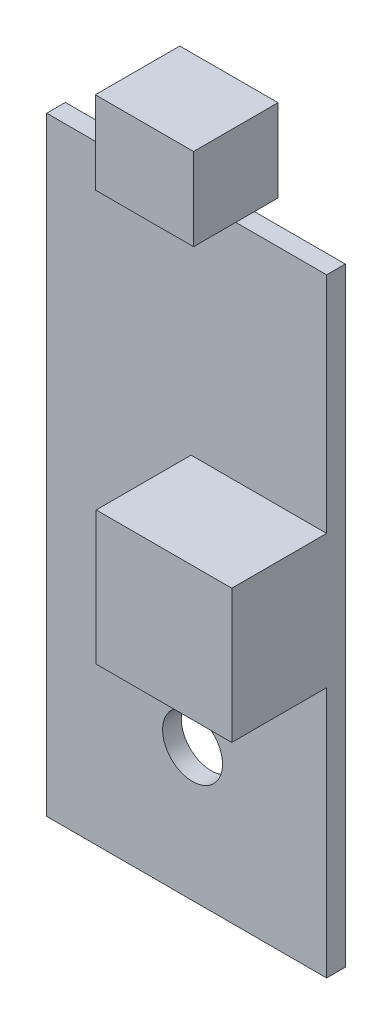
SolidWorks part; units mm, degrees
ref_plane "Front Plane" through (0, 0, 0) normal (0, 0, 1) x (1, 0, 0)
ref_plane "Top Plane" through (0, 0, 0) normal (0, 1, 0) x (1, 0, 0)
ref_plane "Right Plane" through (0, 0, 0) normal (1, 0, 0) x (0, 0, -1)
sketch "Sketch1" plane through (0, 0, 0) normal (0, 0, 1) x (1, 0, 0)
  line L0 (-7.125, 15.5) -> (-2.5, 15.5)
  line L1 (-7.125, 15.5) -> (7.125, 15.5)
  line L2 (-7.125, 15.5) -> (-7.125, -15.5)
  line L3 (-7.125, -15.5) -> (7.125, -15.5)
  line L4 (7.125, 15.5) -> (7.125, -15.5)
  line L5 (-2.5, 15.5) -> (2.5, 15.5)
  line L6 (2.5, 15.5) -> (7.125, 15.5)
  line L7 (-2.5, 15.5) -> (-2.5, 19.7)
  line L8 (-2.5, 15.5) -> (2.5, 15.5)
  line L12 (-2.5, 19.7) -> (2.5, 19.7)
  line L13 (2.5, 19.7) -> (2.5, 15.5)
  point P0 (0, 0)
  dimension "D1" = 14.25
  dimension "D2" = 31
  dimension "D3" = 4.625
  dimension "D4" = 4.625
  dimension "D5" = 5
  dimension "D6" = 4.2
extrude "Boss-Extrude1" add sketch "Sketch1" against normal blind 0.95 contours L4 L1 L0 L2 L3 region at (0, 0, 0)
extrude "Boss-Extrude2" add sketch "Sketch1<4>" against normal mid plane 4.3 contours L13 L12 L7 L1 region at (0, 17.6, 0)
sketch "Sketch1<4>" plane through (0, 0, 0) normal (0, 0, 1) x (1, 0, 0) same geometry as "Sketch1"
sketch "Sketch3" plane through (0, 0, 0) normal (0, 0, 1) x (1, 0, 0)
  line L0 (7.125, 15.5) -> (7.125, 4.1)
  line L1 (7.125, 15.5) -> (7.125, -15.5) construction
  line L2 (7.125, 4.1) -> (7.125, -2.7)
  line L3 (7.125, 4.1) -> (0.225, 4.1)
  line L4 (0.225, 4.1) -> (0.225, -2.7)
  line L5 (0.225, -2.7) -> (7.125, -2.7)
  line M4 (7.125, -15.5) -> (7.125, 15.5)
  dimension "D1" = 11.4
  dimension "D2" = 6.8
  dimension "D3" = 6.9
extrude "Boss-Extrude3" add sketch "Sketch3" along normal blind 4.83 contours L4 L5 L3 M4 region at (3.675, 0.7, 0)
sketch "Sketch4" plane through (0, 0, 0) normal (0, 0, 1) x (1, 0, 0)
  line L0 (-7.125, -15.5) -> (-1.225, -15.5)
  line L6 (-7.125, -15.5) -> (7.125, -15.5) construction
  line L8 (7.125, -15.5) -> (1.825, -15.5)
  circle A0 centre (0.3, -8.725) radius 1.525
  dimension "D1" = 5.9
  dimension "D2" = 5.3
extrude "Cut-Extrude1" cut sketch "Sketch4" against normal through all contours A0 region at (0.3, -8.725, 0)
